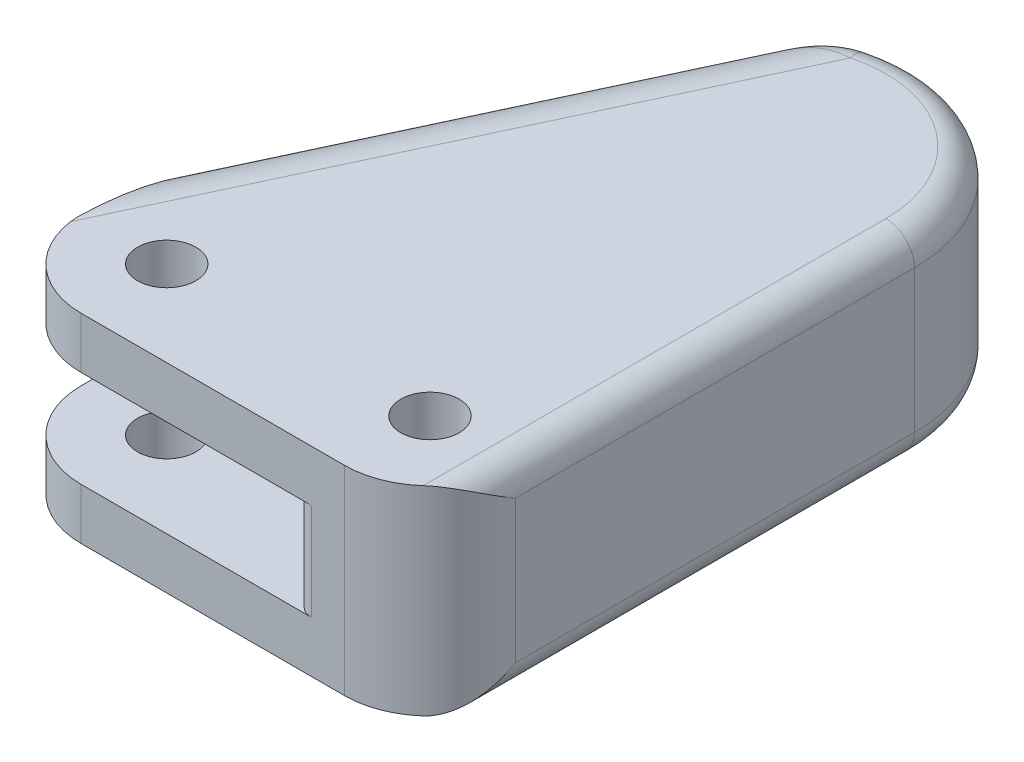
SolidWorks part; units mm, degrees
ref_plane "Front Plane" through (0, 0, 0) normal (0, 0, 1) x (1, 0, 0)
ref_plane "Top Plane" through (0, 0, 0) normal (0, 1, 0) x (1, 0, 0)
ref_plane "Right Plane" through (0, 0, 0) normal (1, 0, 0) x (0, 0, -1)
sketch "Sketch1" plane through (0, 0, 0) normal (0, 1, 0) x (1, 0, 0)
  line L0 (0, 0) -> (11.7323, 0)
  line L2 (15.5423, 17.78) -> (15.5423, 0)
  line L3 (-3.81, 5.08) -> (-3.81, 0)
  line L4 (0, -3.81) -> (11.7323, -3.81)
  line L5 (5.399, 3.3426) -> (9.8273, -3.81)
  line L7 (2.47, 20.6808) -> (-2.9018, 9.1728)
  circle A0 centre (0, 0) radius 1.3
  circle A1 centre (11.7323, 0) radius 1.3
  arc A2 (-3.81, 0) -> (0, -3.81) centre (0, 0) ccw
  arc A3 (11.7323, -3.81) -> (15.5423, 0) centre (11.7323, 0) ccw
  arc A4 (5.08, -3.81) -> (-3.81, 5.08) centre (0, 0) ccw
  arc A5 (2.47, 20.6808) -> (15.5423, 17.78) centre (8.6843, 17.78) cw
  arc A6 (-2.9018, 9.1728) -> (-3.81, 5.08) centre (5.8661, 5.08) ccw
  dimension "D2" = 2.6
  dimension "D3" = 3.81
  dimension "D6" = 6.35
  dimension "D5" = 6.858
  dimension "D1" = 11.7323
  dimension "D4" = 17.78
  dimension "D7" = 1.905
  dimension "D8" = 12.7
extrude "Boss-Extrude1" add sketch "Sketch1" along normal blind 6.604 contours L4 A4 A0 L3 A2 | A4 L4 L5 L0 | A4 L0 L5 | A4 L5 A1 L4 A3 L2 L3 region at (1.1179, 0, -1.1179) region at (6.5949, 0, -0.8622) region at (7.3567, 0, 2.3278) region at (8.1092, 0, -11.3815)
extrude "Cut-Extrude1" cut sketch "Sketch1<3>" along normal blind 4.318 contours A4 L4 L5 L0 | A4 L0 L5 | L4 A4 A0 L3 A2 region at (1.1179, 0, -1.1179) region at (6.5949, 0, -0.8622) region at (7.3567, 0, 2.3278)
sketch "Sketch1<3>" plane through (0, 0, 0) normal (0, 1, 0) x (1, 0, 0) same geometry as "Sketch1"
extrude "Boss-Extrude2" add sketch "Sketch1<4>" against normal blind 2.286 contours L4 A4 A0 L3 A2 | A4 L5 A1 L4 A3 L2 L3 | A4 L4 L5 L0 | A4 L0 L5 region at (1.1179, 0, -1.1179) region at (6.5949, 0, -0.8622) region at (7.3567, 0, 2.3278) region at (8.1092, 0, -11.3815)
sketch "Sketch1<4>" plane through (0, 0, 0) normal (0, 1, 0) x (1, 0, 0) same geometry as "Sketch1"
fillet "Fillet3" radius 3.302 2 edges at (-0.2159, -2.286, -14.9268) (-0.2159, 6.604, -14.9268) tangent propagation no
fillet "Fillet4" radius 1.27 6 edges at (15.5423, -2.286, -8.89) (15.5423, 6.604, -8.89) (13.2638, -2.286, -22.8849) (13.2638, 6.604, -22.8849) (4.6506, 5.5212, -23.3263) (4.6506, -1.2032, -23.3263) tangent propagation no
fillet "Fillet6" radius 0.762 2 edges at (9.8273, 2.159, 3.81) (-3.81, 2.159, -5.08)
